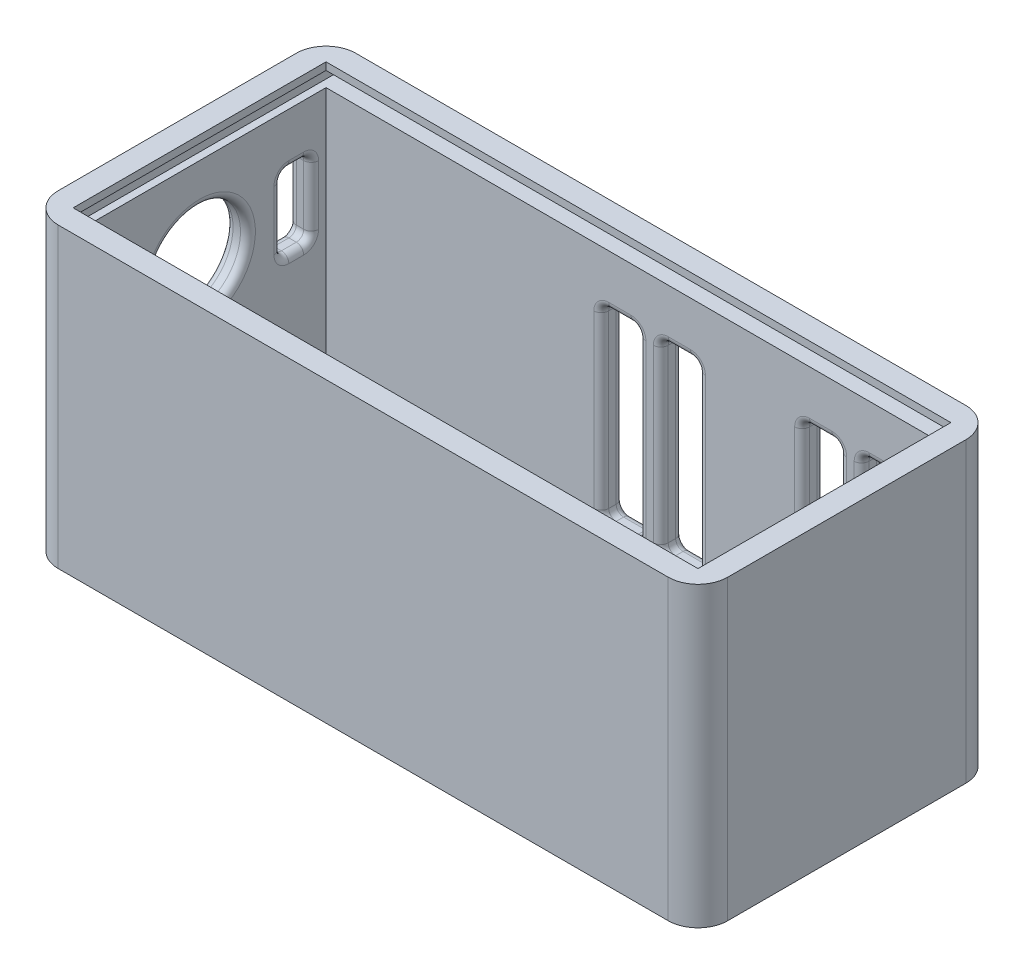
SolidWorks part; units mm, degrees
ref_plane "Alzado" through (0, 0, 0) normal (0, 0, 1) x (1, 0, 0)
ref_plane "Planta" through (0, 0, 0) normal (0, 1, 0) x (1, 0, 0)
ref_plane "Vista lateral" through (0, 0, 0) normal (1, 0, 0) x (0, 0, -1)
sketch "Croquis1" plane through (0, 0, 0) normal (0, 1, 0) x (1, 0, 0)
  line L1 (45, -20) -> (-45, -20)
  line L2 (45, -20) -> (45, 20)
  line L3 (45, 20) -> (-45, 20)
  line L4 (-45, -20) -> (-45, 20)
  line L5 (45, -20) -> (-45, 20) construction
  line L6 (45, 20) -> (-45, -20) construction
  point P0 (0, 0)
  dimension "D1" = 90
  dimension "D2" = 40
extrude "Saliente-Extruir1" add sketch "Croquis1" along normal blind 40
sketch "Croquis2" plane through (0, 40, 0) normal (0, 1, 0) x (1, 0, 0)
  line L0 (45, -20) -> (45, 20) construction
  line L1 (-42, -17) -> (42, -17)
  line L2 (-42, -17) -> (-42, 17)
  line L3 (-42, 17) -> (42, 17)
  line L4 (42, -17) -> (42, 17)
  line L5 (-42, -17) -> (42, 17) construction
  line L6 (-42, 17) -> (42, -17) construction
  line L7 (45, 20) -> (-45, 20) construction
  point P0 (0, 0)
  dimension "D1" = 3
  dimension "D2" = 3
extrude "Cortar-Extruir1" cut sketch "Croquis2" against normal blind 38
sketch "Croquis5" plane through (0, 0, -20) normal (0, 0, -1) x (-1, 0, 0)
  line L11 (-45, 40) -> (-45, 0) construction
  line L12 (43, 37) -> (-43, 37)
  line L13 (43, 37) -> (43, 39)
  line L14 (43, 39) -> (-43, 39)
  line L15 (-43, 37) -> (-43, 39)
  line L16 (45, 40) -> (45, 0) construction
  line L17 (-45, 40) -> (45, 40) construction
  dimension "D1" = 2
  dimension "D2" = 2
  dimension "D3" = 1
  dimension "D4" = 2
extrude "Cortar-Extruir2" cut sketch "Croquis5" against normal blind 38
sketch "Croquis6" plane through (-45, 0, 0) normal (-1, 0, 0) x (0, 0, 1)
  line L0 (-20, 40) -> (-20, 0) construction
  line L1 (-15, 20) -> (-11, 20)
  line L2 (-15, 20) -> (-15, 30)
  line L3 (-15, 30) -> (-11, 30)
  line L4 (-11, 20) -> (-11, 30)
  line L5 (-20, 0) -> (20, 0) construction
  dimension "D1" = 10
  dimension "D2" = 4
  dimension "D3" = 5
  dimension "D4" = 20
extrude "Cortar-Extruir3" cut sketch "Croquis6" against normal up to next
sketch "Croquis7" plane through (0, 0, -20) normal (0, 0, -1) x (-1, 0, 0)
  line L0 (-45, 40) -> (-45, 0) construction
  line L1 (-35, 30) -> (5, 30)
  line L2 (-35, 30) -> (-35, 5)
  line L3 (-35, 5) -> (5, 5)
  line L4 (5, 30) -> (5, 5)
  line L5 (-45, 0) -> (45, 0) construction
  line L6 (-15, 5) -> (-15, 30)
  line L8 (0, 5) -> (-30, 5)
  line L9 (0, 5) -> (0, 30)
  line L10 (0, 30) -> (-30, 30)
  line L11 (-30, 5) -> (-30, 30)
  line L12 (0, 5) -> (-30, 30) construction
  line L13 (0, 30) -> (-30, 5) construction
  line L14 (-3, 5) -> (-27, 5)
  line L15 (-3, 5) -> (-3, 30)
  line L16 (-3, 30) -> (-27, 30)
  line L17 (-27, 5) -> (-27, 30)
  line L18 (-3, 5) -> (-27, 30) construction
  line L19 (-3, 30) -> (-27, 5) construction
  line L20 (-8, 5) -> (-22, 5)
  line L21 (-8, 5) -> (-8, 30)
  line L22 (-8, 30) -> (-22, 30)
  line L23 (-22, 5) -> (-22, 30)
  line L24 (-8, 5) -> (-22, 30) construction
  line L25 (-8, 30) -> (-22, 5) construction
  point P10 (-15, 17.5)
  point P15 (-15, 17.5)
  point P20 (-15, 17.5)
  dimension "D1" = 10
  dimension "D2" = 5
  dimension "D3" = 40
  dimension "D4" = 25
  dimension "D5" = 5
  dimension "D6" = 3
  dimension "D7" = 5
extrude "Cortar-Extruir4" cut sketch "Croquis7" against normal up to next contours L3 L11 L1 L2 | L8 L23 L10 L17 | L21 L14 L15 L16 | L9 L3 L4 L1 region at (32.5, 17.5, -20) region at (24.5, 17.5, -20) region at (5.5, 17.5, -20) region at (-2.5, 17.5, -20)
sketch "Croquis8" plane through (42, 0, 0) normal (-1, 0, 0) x (0, 0, 1)
  line L0 (0, 0) -> (0, 37) construction
  line L1 (17, 37) -> (-17, 37) construction
  line L2 (0, 18.5) -> (-11.8809, 18.5) construction
  line L4 (-12.5, 8.5) -> (12.5, 8.5)
  line L5 (-12.5, 8.5) -> (-12.5, 28.5)
  line L6 (-12.5, 28.5) -> (12.5, 28.5)
  line L7 (12.5, 8.5) -> (12.5, 28.5)
  line L8 (-12.5, 8.5) -> (12.5, 28.5) construction
  line L9 (-12.5, 28.5) -> (12.5, 8.5) construction
  dimension "D1" = 25
  dimension "D2" = 20
extrude "Cortar-Extruir5" cut sketch "Croquis8" against normal blind 1
fillet "Redondeo2" radius 4 4 edges at (45, 20, 20) (45, 20, -20) (-45, 20, -20) (-45, 20, 20)
fillet "Redondeo5" radius 1 46 edges at (-2.5, 5, -17) (-2.5, 30, -17) (-2.5, 30, -20) (-2.5, 5, -20) (5.5, 30, -17) (5.5, 30, -20) (24.5, 5, -20) (24.5, 5, -17) (32.5, 30, -17) (32.5, 30, -20) (32.5, 5, -20) (32.5, 5, -17) (24.5, 30, -17) (24.5, 30, -20) (35, 5, -18.5) (35, 17.5, -20) (35, 30, -18.5) (35, 17.5, -17) (27, 17.5, -17) (27, 5, -18.5) (27, 17.5, -20) (27, 30, -18.5) (8, 17.5, -17) (8, 5, -18.5) (8, 17.5, -20) (8, 30, -18.5) (0, 17.5, -17) (0, 5, -18.5) (0, 17.5, -20) (0, 30, -18.5) (-5, 17.5, -17) (-5, 30, -18.5) (-5, 17.5, -20) (-5, 5, -18.5) (22, 30, -18.5) (22, 17.5, -20) (22, 5, -18.5) (22, 17.5, -17) (30, 30, -18.5) (30, 17.5, -20) (30, 5, -18.5) (30, 17.5, -17) (3, 30, -18.5) (3, 17.5, -20) (3, 5, -18.5) (3, 17.5, -17)
fillet "Redondeo6" radius 1 12 edges at (-42, 25, -11) (-42, 25, -15) (-45, 25, -11) (-43.5, 30, -11) (-42, 30, -13) (-43.5, 30, -15) (-45, 30, -13) (-42, 20, -13) (-43.5, 20, -11) (-45, 20, -13) (-43.5, 20, -15) (-45, 25, -15)
sketch "Croquis9" plane through (-45, 0, 0) normal (-1, 0, 0) x (0, 0, 1)
  line L0 (-10, 25) -> (14.4742, 25) construction
  line L1 (-10, 29) -> (-10, 21) construction
  circle A0 centre (0, 25) radius 6.5
  point P7 (0, 30)
  dimension "D1" = 13
extrude "Cortar-Extruir6" cut sketch "Croquis9" against normal up to next
fillet "Redondeo7" radius 1 2 edges at (-42, 25, 6.5) (-45, 25, 6.5)
